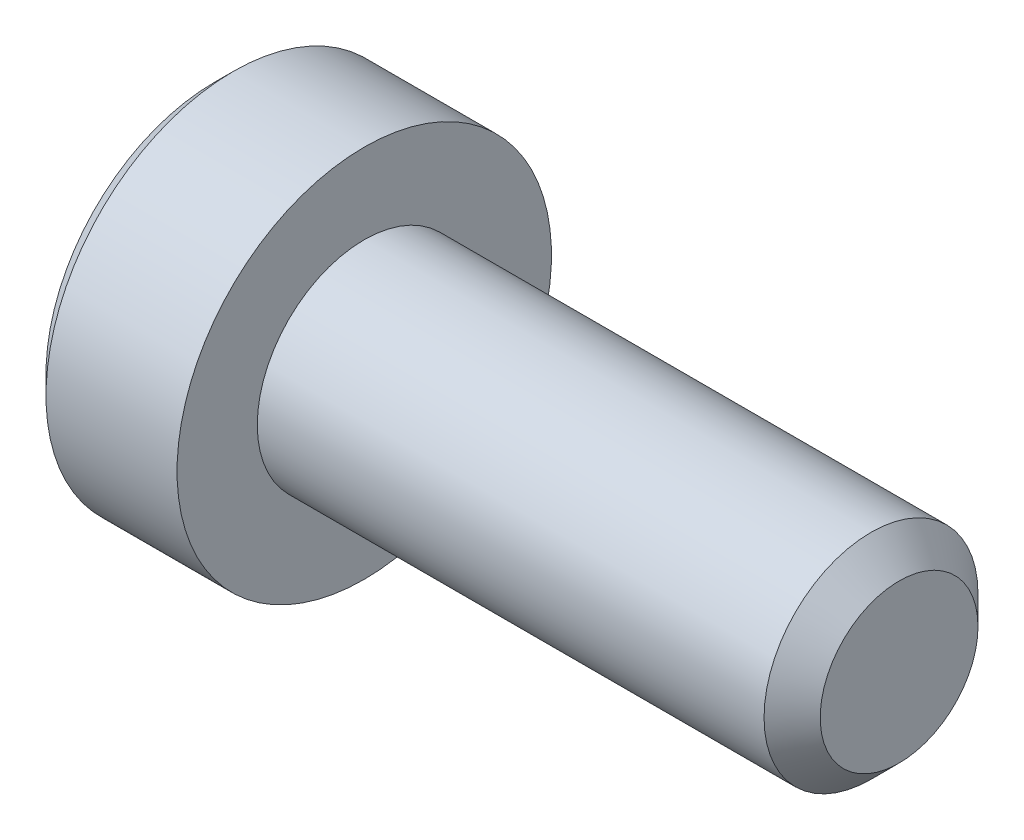
SolidWorks part; units mm, degrees
material "Alloy Steel"
ref_plane "Front Plane" through (0, 0, 0) normal (0, 0, 1) x (1, 0, 0)
ref_plane "Top Plane" through (0, 0, 0) normal (0, 1, 0) x (1, 0, 0)
ref_plane "Right Plane" through (0, 0, 0) normal (1, 0, 0) x (0, 0, -1)
sketch "Sketch1" plane through (0, 0, 0) normal (0, 0, 1) x (1, 0, 0)
  line L0 (5, 0) -> (-5, 0) construction
  line L1 (5, 2) -> (5, -2) construction
  line L2 (-5, 3.5) -> (-5, -3.5) construction
  line L3 (-5, 3.5) -> (-7.45, 3.5) construction
  line L4 (-7.45, 3.5) -> (-7.8, 3.15) construction
  line L5 (-7.8, 3.15) -> (-7.8, -3.15) construction
  line L6 (-7.8, -3.15) -> (-7.45, -3.5) construction
  line L7 (-7.45, -3.5) -> (-5, -3.5) construction
  point P7 (-5.38, 0)
  point P12 (2.2, -2)
  dimension "D1" = 45
  dimension "Dec." = 4
  dimension "Length" = 10
  dimension "Head Dia" = 7
  dimension "Head Height" = 2.8
  dimension "Hex Depth" = 2.42
  dimension "Chamfer" = 0.35
  dimension "D2" = 2.8
ref_plane "Plane1" through (5, 0, 0) normal (1, 0, 0) x (0, 0, -1)
ref_plane "Plane2" through (-7.8, 0, 0) normal (1, 0, 0) x (0, 0, -1)
sketch "Sketch2" plane through (5, 0, 0) normal (1, 0, 0) x (0, 0, -1)
  circle A0 centre (0, 0) radius 2
extrude "Boss-Extrude1" add sketch "Sketch2" against normal up to vertex (10 mm away) up to point (-5, 0, 0)
sketch "Sketch3" plane through (5, 0, 0) normal (1, 0, 0) x (0, 0, -1)
  circle A0 centre (0, 0) radius 2 construction
  circle A1 centre (0, 0) radius 2
curve "Helix/Spiral1" pitch 0.7 height 10.67 turns 15.2429 parameters "Pitch"=0.7
chamfer "Chamfer1" distance 0.525 angle 45 1 edges at (5, 0, -2)
sketch "Sketch5" plane through (0, 0, 0) normal (0, 0, 1) x (1, 0, 0)
  line L0 (5, 2) -> (5.6125, 2)
  line L1 (5.6125, 2) -> (5.35, 1.5453)
  line L2 (5.35, 1.5453) -> (5.2625, 1.5453)
  line L3 (5.2625, 1.5453) -> (5, 2)
  line L4 (5.3063, 1.5453) -> (5.3063, 2) construction
  line L5 (5.1313, 1.7727) -> (5.4813, 1.7727) construction
  dimension "D1" = 60
  dimension "D2" = 0.35
  dimension "D3" = 0.0875
sweep "Cut-Sweep1" [suppressed] cut profiles "Sketch5" path "Helix/Spiral1"
sketch "Sketch4" plane through (-7.8, 0, 0) normal (1, 0, 0) x (0, 0, -1)
  line L0 (-3.5, 0.7937) -> (3.5, 0.7937) construction
  line L1 (0, 1.4434) -> (-1.25, 0.7217)
  line L2 (-1.25, 0.7217) -> (-1.25, -0.7217)
  line L3 (-1.25, -0.7217) -> (0, -1.4434)
  line L4 (0, -1.4434) -> (1.25, -0.7217)
  line L5 (1.25, -0.7217) -> (1.25, 0.7217)
  line L6 (1.25, 0.7217) -> (0, 1.4434)
  line L7 (0, 0) -> (0, 0.7937) construction
  circle A0 centre (0, 0) radius 1.25 construction
  dimension "Hex Size" = 2.5
  dimension "D1" = 7
  dimension "D2" = 0.7937
sketch "Sketch6" plane through (0, 0, 0) normal (0, 0, 1) x (1, 0, 0)
  line L0 (-7.45, 3.5) -> (-7.8, 3.15) construction
  line L1 (-5, 3.5) -> (-7.45, 3.5) construction
  line L2 (-5, 3.5) -> (-5, -3.5) construction
  line L3 (-7.8, 3.15) -> (-7.8, -3.15) construction
  line L4 (-7.45, 3.5) -> (-7.8, 3.15)
  line L5 (-5, 3.5) -> (-7.45, 3.5)
  line L6 (-5, 3.5) -> (-5, 0)
  line L7 (-7.8, 3.15) -> (-7.8, 0)
  line L8 (-5, 0) -> (-7.8, 0) construction
  line L9 (-5, 0) -> (-7.8, 0)
revolve "Revolve1" add sketch "Sketch6" angle 360 about L8
extrude "Cut-Extrude1" cut sketch "Sketch4" along normal up to vertex (2.42 mm away) up to point (-5.38, 0, 0)
sketch "Sketch8" plane through (-7.8, 0, 0) normal (-1, 0, 0) x (0, 0, 1)
  circle A1 centre (0, 0) radius 1.4434
extrude "Cut-Extrude2" cut sketch "Sketch8" against normal through all draft 45
equation "\"D3@Helix/Spiral1\" = \"Length@Sketch1\"+\"Pitch@Helix/Spiral1\"-.03"
equation "\"D3@Sketch5\" = \"Pitch@Helix/Spiral1\"*.125"
equation "\"D2@Sketch5\" = \"Pitch@Helix/Spiral1\"*.50"
equation "\"D1@Chamfer1\" = \"Pitch@Helix/Spiral1\"*.75"
equation "\"D2@Sketch1\" = \"Pitch@Helix/Spiral1\"*4"
equation "\"D1@Sketch4\" = \"Head Dia@Sketch1\""
equation "\"Chamfer@Sketch1\" = \"Head Height@Sketch1\"/8"
